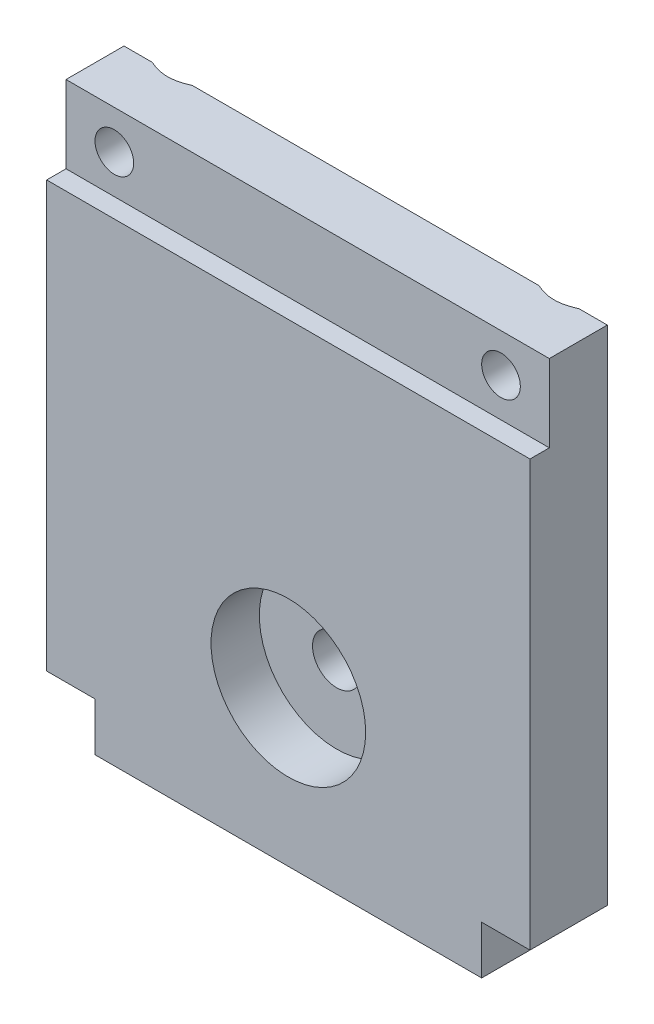
SolidWorks part; units mm, degrees
material "PVC rigide"
ref_plane "Plan de face" through (0, 0, 0) normal (0, 0, 1) x (1, 0, 0)
ref_plane "Plan de dessus" through (0, 0, 0) normal (0, 1, 0) x (1, 0, 0)
ref_plane "Plan de droite" through (0, 0, 0) normal (1, 0, 0) x (0, 0, -1)
sketch "Esquisse1" plane through (0, 0, 0) normal (0, 0, 1) x (1, 0, 0)
  line L0 (-25, -23.5) -> (-20, -23.5)
  line L1 (-25, 28.5) -> (25, 28.5)
  line L2 (-25, 28.5) -> (-25, -23.5)
  line L3 (-20, -28.5) -> (20, -28.5)
  line L4 (25, 28.5) -> (25, -23.5)
  line L5 (-20, -23.5) -> (-20, -28.5)
  line L6 (25, -23.5) -> (20, -23.5)
  line L7 (20, -23.5) -> (20, -28.5)
  line L8 (25, -28.5) -> (25, -23.5) construction
  line L9 (25, -28.5) -> (20, -28.5) construction
  line L10 (-25, -23.5) -> (-25, -28.5) construction
  line L11 (-25, -28.5) -> (-20, -28.5) construction
  line L12 (25, 28.5) -> (-25, -28.5) construction
  line L13 (-25, 28.5) -> (25, -28.5) construction
  point P9 (0, 0)
  dimension "D4" = 5
  dimension "D1" = 50
  dimension "D2" = 57
  dimension "D3" = 5
extrude "Boss.-Extru.1" add sketch "Esquisse1" along normal blind 8
sketch "Esquisse2" plane through (0, -28.5, 0) normal (0, -1, 0) x (1, 0, 0)
  line L0 (-25, 4) -> (25, 4) construction
  line L1 (-25, 8) -> (-25, 0) construction
  line L2 (25, 8) -> (25, 0) construction
  circle A0 centre (-15, 4) radius 2
  circle A1 centre (15, 4) radius 2
  dimension "D1" = 4
  dimension "D2" = 10
  dimension "D3" = 10
extrude "Enlèv. mat.-Extru.1" cut sketch "Esquisse2" against normal blind 10
sketch "Esquisse3" plane through (0, 0, 8) normal (0, 0, 1) x (1, 0, 0)
  line L0 (-25.973, 24.5) -> (39.229, 24.5) construction
  line L1 (25, 28.5) -> (-25, 28.5) construction
  line L2 (-25, 28.5) -> (-25, -23.5) construction
  line L3 (25, -23.5) -> (25, 28.5) construction
  circle A0 centre (-20, 24.5) radius 2
  circle A1 centre (20, 24.5) radius 2
  dimension "D2" = 4
  dimension "D1" = 4
  dimension "D3" = 5
  dimension "D4" = 5
extrude "Enlèv. mat.-Extru.2" cut sketch "Esquisse3" against normal through all
chamfer "Chanfrein1" distance 2.5 angle 45 2 edges at (22, 24.5, 0) (-18, 24.5, 0)
sketch "Esquisse4" plane through (0, 0, 8) normal (0, 0, 1) x (1, 0, 0)
  line L0 (-32.372, -12.5) -> (112.9613, -12.5) construction
  line L1 (0, -17.2825) -> (0, 28.5) construction
  line L3 (-20, -28.5) -> (20, -28.5) construction
  line L4 (25, 28.5) -> (-25, 28.5) construction
  circle A0 centre (0, -12.5) radius 8
  point P17 (0, -12.5)
  dimension "D1" = 16
  dimension "D2" = 16
extrude "Enlèv. mat.-Extru.3" cut sketch "Esquisse4" against normal blind 5
sketch "Esquisse5" plane through (0, 0, 3) normal (0, 0, 1) x (1, 0, 0)
  circle A0 centre (0, -12.5) radius 2.5
  circle A1 centre (0, -12.5) radius 8 construction
  dimension "D1" = 5
extrude "Enlèv. mat.-Extru.4" cut sketch "Esquisse5" against normal through all
sketch "Esquisse6" plane through (0, 0, 8) normal (0, 0, 1) x (1, 0, 0)
  line L0 (25, -23.5) -> (25, 28.5) construction
  line L1 (-25, 28.5) -> (25, 28.5)
  line L2 (-25, 28.5) -> (-25, 20.5)
  line L3 (-25, 20.5) -> (25, 20.5)
  line L4 (25, 28.5) -> (25, 20.5)
  circle A0 centre (-20, 24.5) radius 2 construction
  dimension "D1" = 4
extrude "Enlèv. mat.-Extru.5" cut sketch "Esquisse6" against normal blind 2
